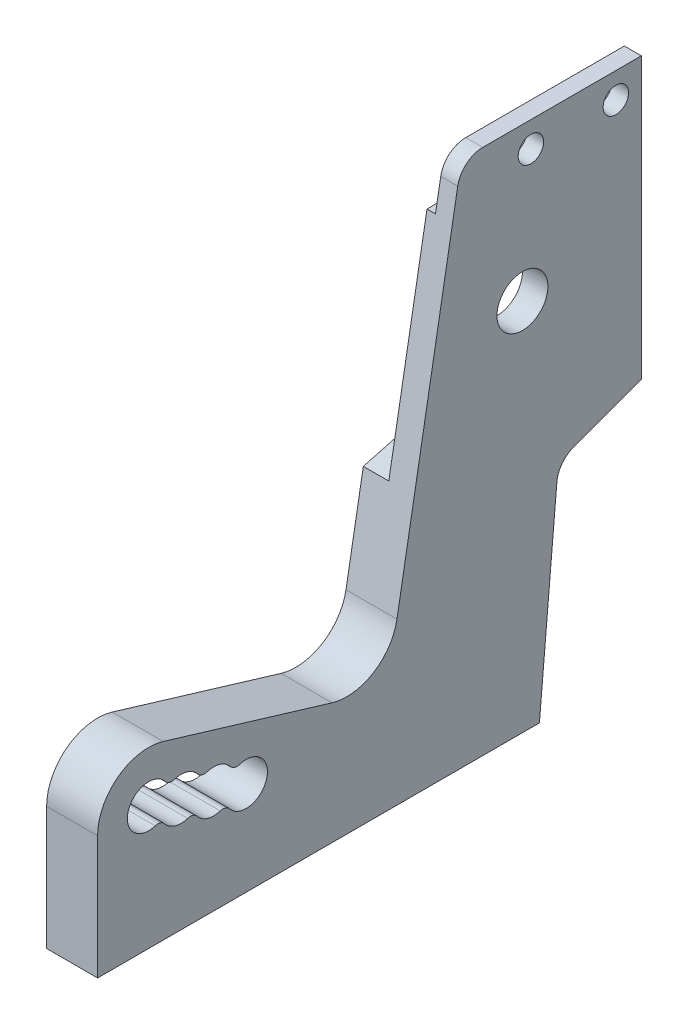
SolidWorks part; units mm, degrees
material "1060 Alloy"
ref_plane "Front Plane" through (0, 0, 0) normal (0, 0, 1) x (1, 0, 0)
ref_plane "Top Plane" through (0, 0, 0) normal (0, 1, 0) x (1, 0, 0)
ref_plane "Right Plane" through (0, 0, 0) normal (1, 0, 0) x (0, 0, -1)
sketch "Sketch1" plane through (0, 0, 0) normal (1, 0, 0) x (0, 0, -1)
  line L1 (0, 0) -> (64, 0)
  line L2 (0, 0) -> (0, 62)
  line L3 (0, 62) -> (64, 62)
  line L4 (64, 0) -> (64, 62)
  circle A0 centre (6, 14.5) radius 2.5
  circle A1 centre (50, 44) radius 3
  dimension "D1" = 6
  dimension "D2" = 5
  dimension "D3" = 14.5
  dimension "D4" = 6
  dimension "D5" = 44
  dimension "D6" = 50
  dimension "D7" = 64
  dimension "D8" = 62
extrude "Boss-Extrude1" add sketch "Sketch1" along normal blind 6
sketch "Sketch2" plane through (6, 0, 0) normal (1, 0, 0) x (0, 0, -1)
  line L0 (0, 62) -> (0, 0) construction
  line L1 (0, 0) -> (64, 0) construction
  line L2 (7.7322, 20.2445) -> (27.5931, 14.2555)
  line L4 (0, 14.5) -> (0, 63)
  line L5 (0, 63) -> (43, 63)
  line L6 (43, 63) -> (35.2342, 18.9581)
  line L7 (64, 62) -> (0, 62) construction
  arc A0 (0, 14.5) -> (7.7322, 20.2445) centre (6, 14.5) cw
  circle A1 centre (50, 44) radius 5 construction
  circle A2 centre (6, 14.5) radius 2.5 construction
  arc A4 (27.5931, 14.2555) -> (35.2342, 18.9581) centre (29.3254, 20) ccw
  dimension "D2" = 10
  dimension "D4" = 80
  dimension "D1" = 1
  dimension "D3" = 43
  dimension "D5" = 20
extrude "Cut-Extrude1" cut sketch "Sketch2" against normal up to next
sketch "Sketch3" plane through (6, 0, 0) normal (1, 0, 0) x (0, 0, -1)
  line L2 (0, 0) -> (64, 0) construction
  line L57 (64, 0) -> (52, 0)
  line L58 (64, 0) -> (64, 29)
  line L59 (64, 29) -> (54.2259, 25.4425)
  line L60 (52, 0) -> (54.2259, 25.4425)
  dimension "D1" = 52
  dimension "D2" = 29
  dimension "D3" = 70
  dimension "D4" = 85
extrude "Cut-Extrude2" cut sketch "Sketch3" against normal up to next
fillet "Fillet1" radius 3 1 edges at (3, 62, -42.8237)
fillet "Fillet2" radius 3 1 edges at (3, 25.4425, -54.2259)
hole_wizard "Tap Drill for M3 Tap1" positions "Sketch5" profile "Sketch4" hole size "M3" standard "ISO"
sketch "Sketch5" plane through (0, 0, 0) normal (0, -1, 0) x (-1, 0, 0)
  line L1 (-6, 0) -> (0, 0) construction
  line L2 (-6, 0) -> (-6, 52) construction
  point P0 (-3, 46)
  point P2 (-3, 10)
  dimension "D1" = 3
  dimension "D2" = 10
  dimension "D3" = 36
sketch "Sketch4" plane through (3, 0, -46) normal (1, 0, 0) x (0, 0, -1)
  line L0 (0, 0) -> (0, 9.7511)
  line L1 (0, 9.7511) -> (1.25, 9)
  line L2 (1.25, 9) -> (1.25, 0)
  line L5 (1.25, 0) -> (0, 0)
  line L10 (0, 9.7511) -> (-1.25, 9) construction
  line L11 (0, -6.35) -> (0, 107.95) construction
  dimension "Hole Dia." = 2.5
  dimension "Hole Depth" = 9
  dimension "Drill Angle" = 118
sketch "Sketch9" plane through (0, 0, 0) normal (-1, 0, 0) x (0, 0, 1)
  line L0 (-64, 62) -> (-64, 35)
  line L1 (-64, 62) -> (-45.341, 62) construction
  line L3 (-64, 29) -> (-64, 62) construction
  line L4 (-64, 62) -> (-42.8237, 62)
  line L5 (-42.8237, 62) -> (-37.2725, 30.5179)
  line L6 (-54, 35) -> (-64, 35)
  line L11 (-35.2342, 18.9581) -> (-42.3865, 59.5209) construction
  line L12 (-37.2725, 30.5179) -> (-54, 35)
  dimension "D1" = 10
  dimension "D2" = 27
  dimension "D5" = 65
extrude "Cut-Extrude3" cut sketch "Sketch9" against normal blind 3
sketch "Sketch10" plane through (3, 0, 0) normal (-1, 0, 0) x (0, 0, 1)
  line L0 (-45.341, 62) -> (-64, 62) construction
  line L1 (-64, 62) -> (-64, 35) construction
  circle A0 centre (-61, 59) radius 1.5
  circle A1 centre (-51, 59) radius 1.5
  dimension "D1" = 3
  dimension "D2" = 3
  dimension "D3" = 3
  dimension "D4" = 10
extrude "Cut-Extrude4" cut sketch "Sketch10" against normal up to next
sketch "Sketch11" plane through (0, 0, 0) normal (-1, 0, 0) x (0, 0, 1)
  line L0 (-6, 14.5) -> (-25.8609, 8.511) construction
  line L1 (-7.7322, 20.2445) -> (-27.5931, 14.2555) construction
  circle A0 centre (-9.8297, 13.3452) radius 2.5
  circle A1 centre (-6, 14.5) radius 2.5 construction
  dimension "D1" = 4
extrude "Cut-Extrude5" cut sketch "Sketch11" against normal up to next
pattern_linear "LPattern1" count 3 spacing 4 along (0, -0.2887, -0.9574) of "Cut-Extrude5"
fillet "Fillet3" radius 1 6 edges at (3, 12.4865, -7.4818) (3, 11.3316, -11.3114) (3, 10.1768, -15.1411) (3, 15.3587, -8.3479) (3, 14.2039, -12.1776) (3, 13.0491, -16.0072)
sketch "Sketch12" plane through (3, 0, 0) normal (-1, 0, 0) x (0, 0, 1)
  line L1 (-64, 62) -> (-41.0174, 62)
  line L2 (-64, 62) -> (-64, 56)
  line L3 (-64, 56) -> (-41.0174, 56)
  line L4 (-41.0174, 62) -> (-41.0174, 56)
  dimension "D1" = 6
extrude "Cut-Extrude6" cut sketch "Sketch12" against normal blind 1
